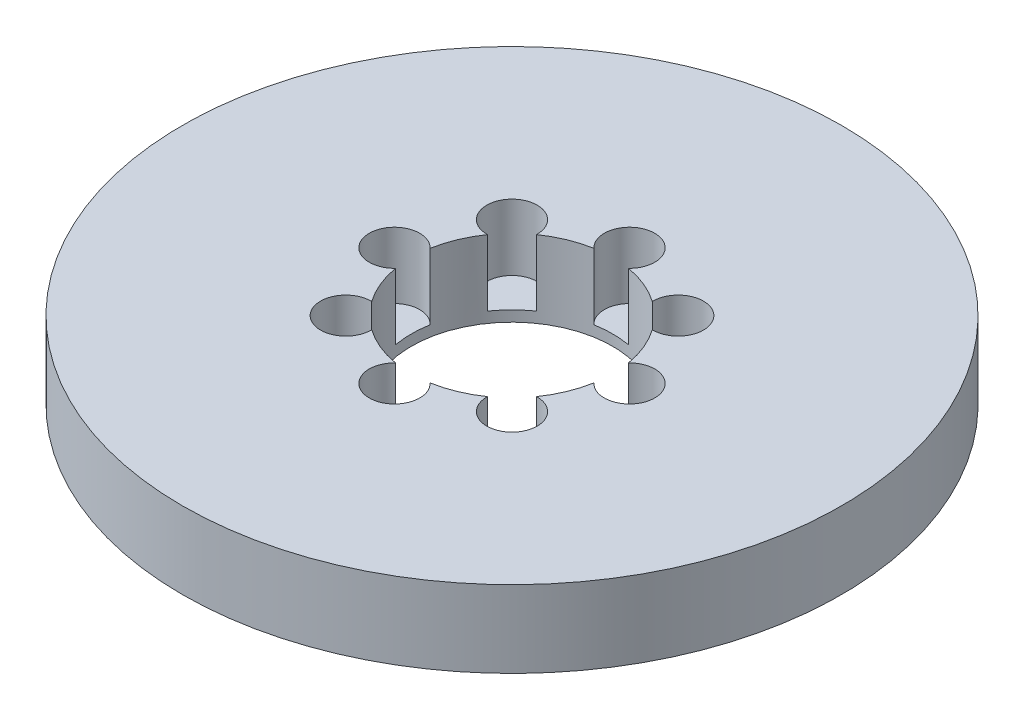
SolidWorks part; units mm, degrees
ref_plane "Front Plane" through (0, 0, 0) normal (0, 0, 1) x (1, 0, 0)
ref_plane "Top Plane" through (0, 0, 0) normal (0, 1, 0) x (1, 0, 0)
ref_plane "Right Plane" through (0, 0, 0) normal (1, 0, 0) x (0, 0, -1)
sketch "Sketch1" plane through (0, 0, 0) normal (0, 1, 0) x (1, 0, 0)
  circle A0 centre (0, 0) radius 90
  dimension "FLANGE_OD" = 180
extrude "Boss-Extrude1" add sketch "Sketch1" along normal blind 21
sketch "Sketch2" plane through (0, 0, 0) normal (0, 1, 0) x (1, 0, 0)
  circle A0 centre (0, 0) radius 27.5
  dimension "BORE_D" = 55
extrude "Cut-Extrude1" cut sketch "Sketch2" along normal through all
sketch "Sketch3" plane through (0, 21, 0) normal (0, 1, 0) x (1, 0, 0)
  circle A0 centre (0, 0) radius 32.0946 construction
  circle A1 centre (-32.0946, 0) radius 6.8826
  dimension "BOLT_D" = 13.7652
  dimension "BOLT_PCD" = 64.1893
extrude "Cut-Extrude2" cut sketch "Sketch3" against normal blind 18.0692
pattern_circular "CirPattern1" count 8 over 360 about axis through (0, 0, 0) along (0, 1, 0) of "Cut-Extrude2"
